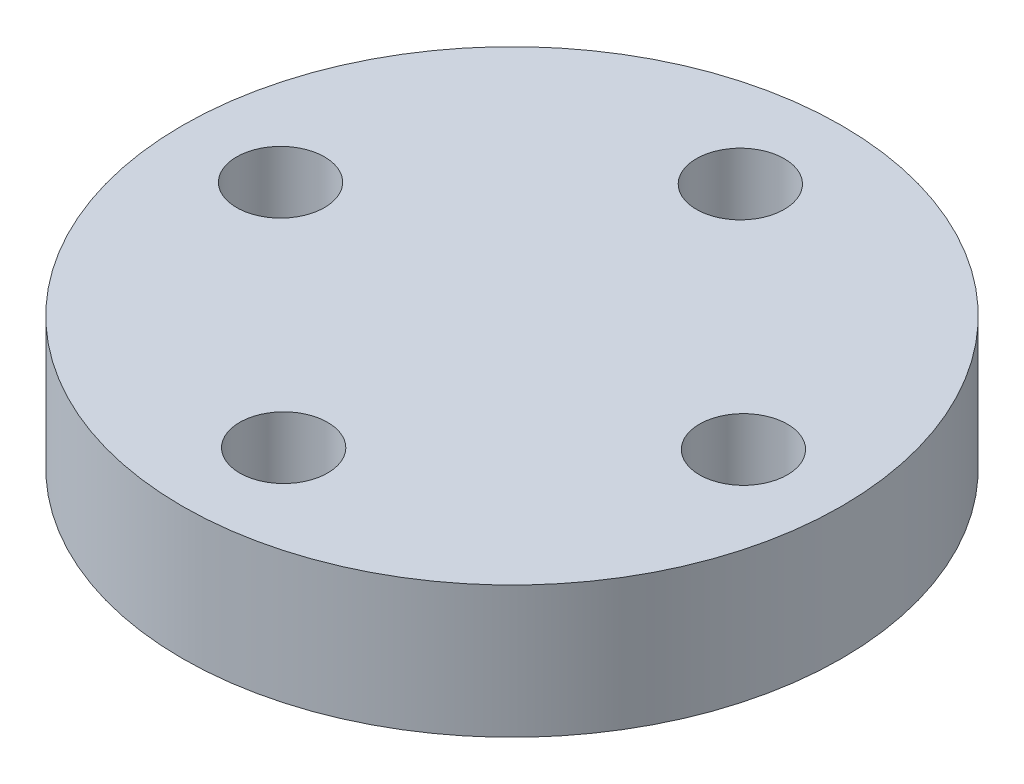
SolidWorks part; units mm, degrees
ref_plane "Front Plane" through (0, 0, 0) normal (0, 0, 1) x (1, 0, 0)
ref_plane "Top Plane" through (0, 0, 0) normal (0, 1, 0) x (1, 0, 0)
ref_plane "Right Plane" through (0, 0, 0) normal (1, 0, 0) x (0, 0, -1)
sketch "Sketch1" plane through (0, 0, 0) normal (0, 1, 0) x (1, 0, 0)
  line L0 (0, 75) -> (0, -75) construction
  line L1 (-75, 0) -> (75, 0) construction
  circle A0 centre (0, 0) radius 75
  circle A1 centre (0, -51.9403) radius 10
  circle A2 centre (52.6486, 0) radius 10
  circle A3 centre (-52.6486, 0) radius 10
  circle A4 centre (0, 51.9403) radius 10
extrude "Boss-Extrude1" add sketch "Sketch1" against normal blind 30
sketch "Sketch2" plane through (0, -30, 0) normal (0, -1, 0) x (1, 0, 0)
  circle A0 centre (0, 0) radius 20
extrude "Boss-Extrude2" add sketch "Sketch2" along normal blind 30
sketch "Sketch3" plane through (0, -60, 0) normal (0, -1, 0) x (1, 0, 0)
  line L1 (2.1309, 4.0979) -> (-2.4834, 3.8944)
  line L2 (-2.4834, 3.8944) -> (-4.6143, -0.2035)
  line L3 (-4.6143, -0.2035) -> (-2.1309, -4.0979)
  line L4 (-2.1309, -4.0979) -> (2.4834, -3.8944)
  line L5 (2.4834, -3.8944) -> (4.6143, 0.2035)
  line L6 (4.6143, 0.2035) -> (2.1309, 4.0979)
  circle A0 centre (0, 0) radius 4 construction
extrude "Boss-Extrude5" add sketch "Sketch3" against normal through all
extrude "Cut-Extrude1" cut sketch "Sketch3<3>" against normal blind 23
sketch "Sketch3<3>" plane through (0, -60, 0) normal (0, -1, 0) x (1, 0, 0) same geometry as "Sketch3"
